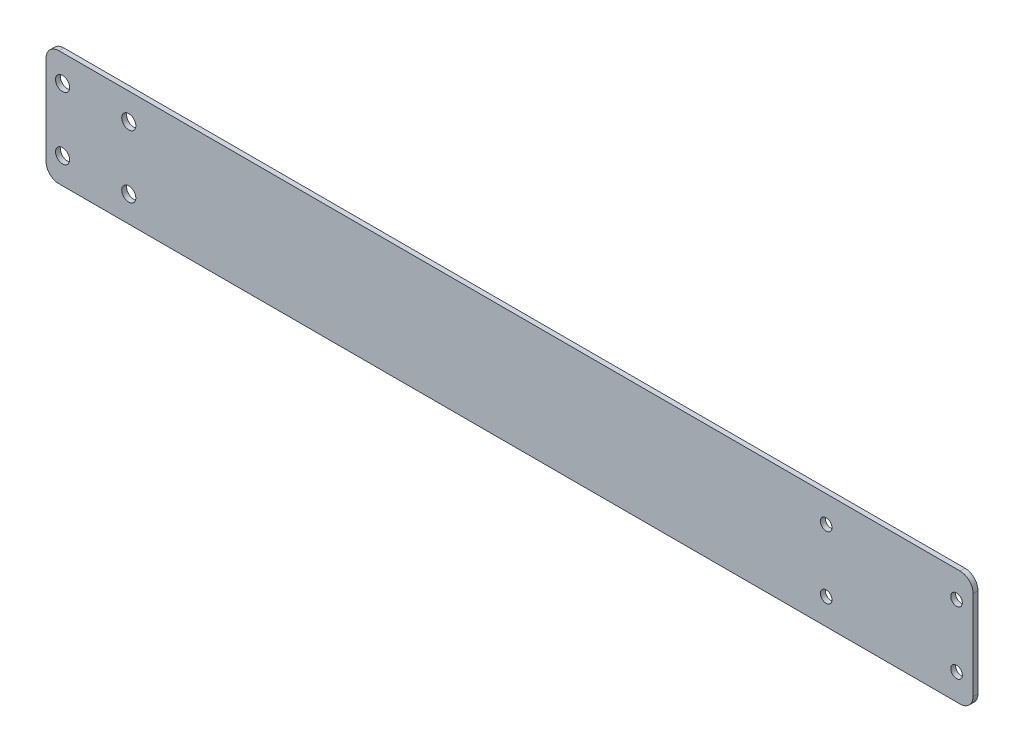
SolidWorks part; units mm, degrees
ref_plane "Front Plane" through (0, 0, 0) normal (0, 0, 1) x (1, 0, 0)
ref_plane "Top Plane" through (0, 0, 0) normal (0, 1, 0) x (1, 0, 0)
ref_plane "Right Plane" through (0, 0, 0) normal (1, 0, 0) x (0, 0, -1)
sketch "Sketch1" plane through (0, 0, 0) normal (0, 0, 1) x (1, 0, 0)
  line L0 (355.6, 34) -> (0, 34) construction
  line L1 (0, 0) -> (355.6, 0)
  line L2 (0, 0) -> (0, 44.196)
  line L3 (0, 44.196) -> (355.6, 44.196)
  line L4 (355.6, 0) -> (355.6, 44.196)
  line L5 (355.6, 10) -> (0, 10) construction
  line L6 (349.25, 44.196) -> (349.25, 0) construction
  line L7 (299.25, 44.196) -> (299.25, 0) construction
  line L8 (6.35, 44.196) -> (6.35, 0) construction
  line L11 (31.75, 44.196) -> (31.75, 0) construction
  circle A0 centre (299.25, 10) radius 2.2225
  circle A1 centre (349.25, 10) radius 2.2225
  circle A2 centre (349.25, 34) radius 2.2225
  circle A3 centre (299.25, 34) radius 2.2225
  circle A8 centre (6.35, 34) radius 2.7051
  circle A9 centre (31.75, 34) radius 2.7051
  circle A10 centre (6.35, 10) radius 2.7051
  circle A11 centre (31.75, 10) radius 2.7051
  dimension "D7" = 4.445
  dimension "D10" = 5.4102
  dimension "D1" = 44.196
  dimension "D2" = 355.6
  dimension "D3" = 50
  dimension "D4" = 24
  dimension "D5" = 10
  dimension "D6" = 6.35
  dimension "D8" = 25.4
  dimension "D9" = 6.35
base flange "Base-Flange1" sketch "Sketch1" thickness 1.8796 reverse thickness direction no parameters "D1"=0.7366
fillet "Fillet1" radius 5 4 edges at (0, 0, -0.9398) (0, 44.196, -0.9398) (355.6, 0, -0.9398) (355.6, 44.196, -0.9398)
sketch "Bend-Lines1" [suppressed] plane through (0, 0, 0) normal (0, 1, 0) x (1, 0, 0)
sketch "Bounding-Box1" [suppressed] plane through (0, 0, 0) normal (0, 1, 0) x (1, 0, 0)
sheet metal parameters "Sheet-Metal1" thickness 1.8796 parameters "D1"=0.7366
flat pattern "Flat-Pattern1" [suppressed]
sketch "Bend-Lines2" plane through (0, 0, 0) normal (0, 1, 0) x (1, 0, 0)
sketch3d "Bounding-Box2" [suppressed]
  line L0 (0, 44.196, 0) -> (355.6, 44.196, 0) construction
  line L1 (0, 0, 0) -> (355.6, 0, 0) construction
  line L2 (0, 44.196, 0) -> (0, 0, 0) construction
  line L3 (355.6, 44.196, 0) -> (355.6, 0, 0) construction
